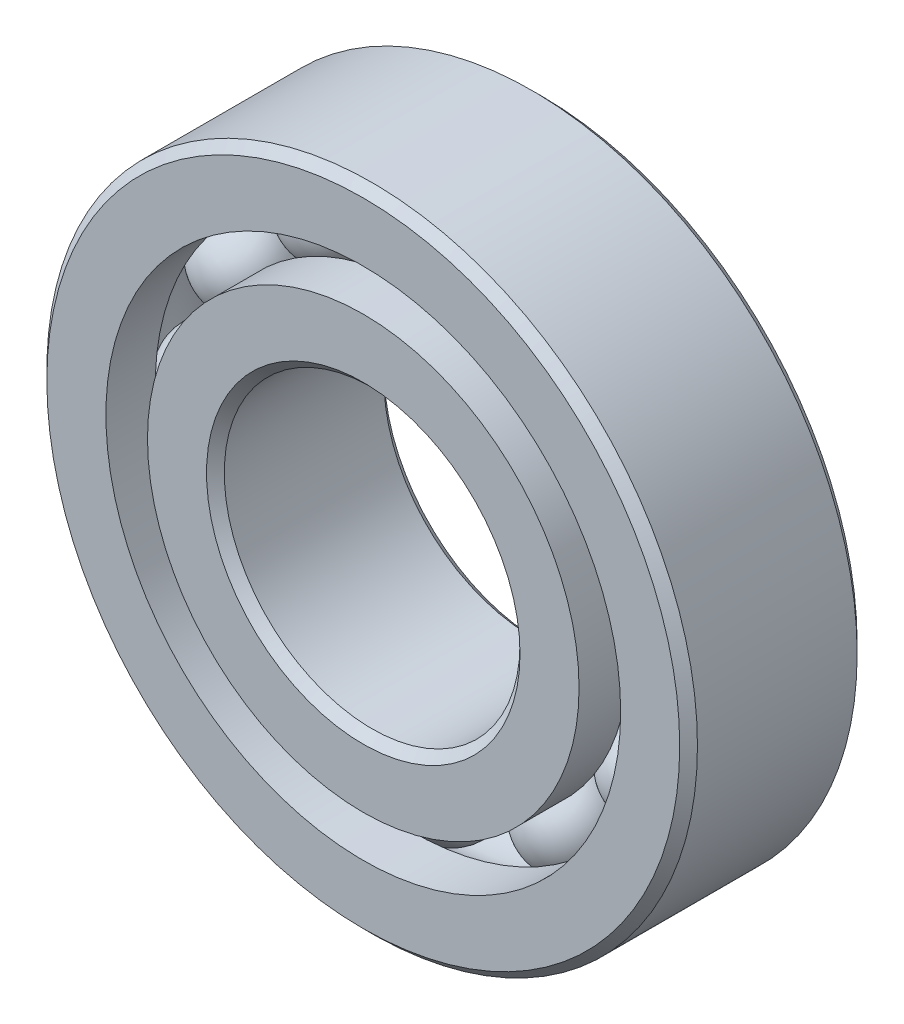
SolidWorks part; units mm, degrees
ref_plane "Front Plane" through (0, 0, 0) normal (0, 0, 1) x (1, 0, 0)
ref_plane "Top Plane" through (0, 0, 0) normal (0, 1, 0) x (1, 0, 0)
ref_plane "Right Plane" through (0, 0, 0) normal (1, 0, 0) x (0, 0, -1)
sketch "Sketch1" plane through (0, 0, 0) normal (1, 0, 0) x (0, 0, -1)
  line L0 (-3, 0) -> (3, 0) construction
  line L1 (0, 11) -> (0, -11) construction
  line L2 (2.7, 11) -> (-2.7, 11)
  line L3 (-2.7, 11) -> (-3, 10.7)
  line L4 (-3, 10.7) -> (-3, 8.7033)
  line L5 (-3, 8.7033) -> (-1.3333, 8.7033)
  line L6 (3, 8.7033) -> (1.3333, 8.7033)
  line L7 (3, 10.7) -> (3, 8.7033)
  line L8 (2.7, 11) -> (3, 10.7)
  line L9 (0, 11) -> (0, 8) construction
  line L10 (0, 8) -> (0, 5) construction
  arc A0 (-1.3333, 8.7033) -> (1.3333, 8.7033) centre (0, 8) cw
  point P14 (0, 5)
  dimension "Width" = 6
  dimension "OD" = 22
  dimension "D1" = 45
  dimension "D2" = 0.3
  dimension "Shaft Dia" = 10
  dimension "D3" = 2.6667
  dimension "D4" = 0.7033
revolve "Revolve1" add sketch "Sketch1" angle 360 about L0
sketch "Sketch3" plane through (0, 0, 0) normal (1, 0, 0) x (0, 0, -1)
  line L0 (-3, 7.2967) -> (-1.3333, 7.2967)
  line L1 (0, 11) -> (0, -11) construction
  line L2 (-3, 10.7) -> (-3, 8.7033) construction
  line L3 (-3, 7.2967) -> (-3, 5.3)
  line L4 (-2.7, 11) -> (-3, 10.7) construction
  line L5 (-3, 5.3) -> (-2.7, 5)
  line L6 (-2.7, 5) -> (2.7, 5)
  line L7 (2.7, 11) -> (2.7, -11) construction
  line L8 (2.7, 5) -> (3, 5.3)
  line L9 (3, -10.7) -> (3, 10.7) construction
  line L10 (3, 5.3) -> (3, 7.2967)
  line L11 (3, 7.2967) -> (1.3333, 7.2967)
  line L13 (2.7, 11) -> (3, 10.7) construction
  arc A0 (1.3333, 8.7033) -> (-1.3333, 8.7033) centre (0, 8) ccw construction
  arc A1 (1.3333, 7.2967) -> (-1.3333, 7.2967) centre (0, 8) cw
revolve "Revolve3" add sketch "Sketch3" angle 360 about L0
sketch "Sketch4" plane through (0, 0, 0) normal (1, 0, 0) x (0, 0, -1)
  line L0 (-1.5074, 8) -> (1.5074, 8)
  arc A2 (-1.5074, 8) -> (1.5074, 8) centre (0, 8) cw
  arc A3 (1.3333, 8.7033) -> (-1.3333, 8.7033) centre (0, 8) ccw construction
revolve "Revolve4" add sketch "Sketch4" angle 360 about L0
ref_axis "Axis1" through (0, 0, -3) along (0, 0, 1)
pattern_circular "CirPattern1" count 12 over 360 about axis through (0, 0, -3) along (0, 0, 1) of bodies 104
sketch "Sketch5" plane through (0, 0, 0) normal (1, 0, 0) x (0, 0, -1)
  line L0 (-3, 8.7033) -> (-1.3333, 8.7033) construction
  line L1 (-2.85, 8.7033) -> (-1.5074, 8.7033)
  line L2 (-2.85, 8.7033) -> (-2.85, 7.2967)
  line L3 (-2.85, 7.2967) -> (-1.5074, 7.2967)
  line L4 (-1.5074, 8.7033) -> (-1.5074, 7.2967)
  line L5 (-3, 7.2967) -> (-1.3333, 7.2967) construction
  line L6 (3, 8.7033) -> (1.3333, 8.7033) construction
  line L7 (2.85, 8.7033) -> (1.5074, 8.7033)
  line L8 (2.85, 8.7033) -> (2.85, 7.2967)
  line L9 (2.85, 7.2967) -> (1.5074, 7.2967)
  line L10 (1.5074, 8.7033) -> (1.5074, 7.2967)
  line L11 (3, 7.2967) -> (1.3333, 7.2967) construction
  line L12 (-2.7, 11) -> (-3, 10.7) construction
  point P18 (-2.85, 10.85)
equation "\"D2@Sketch1\" = \"Width@Sketch1\"*.05"
equation "\"D3@Sketch1\" = \"Width@Sketch1\"/2.25"
equation "\"D4@Sketch1\" = (((\"OD@Sketch1\"-\"Width@Sketch1\")/2)/3.25)/3.5"
equation "\"D2@CirPattern1\" = 360/\"Balls@CirPattern1\""
